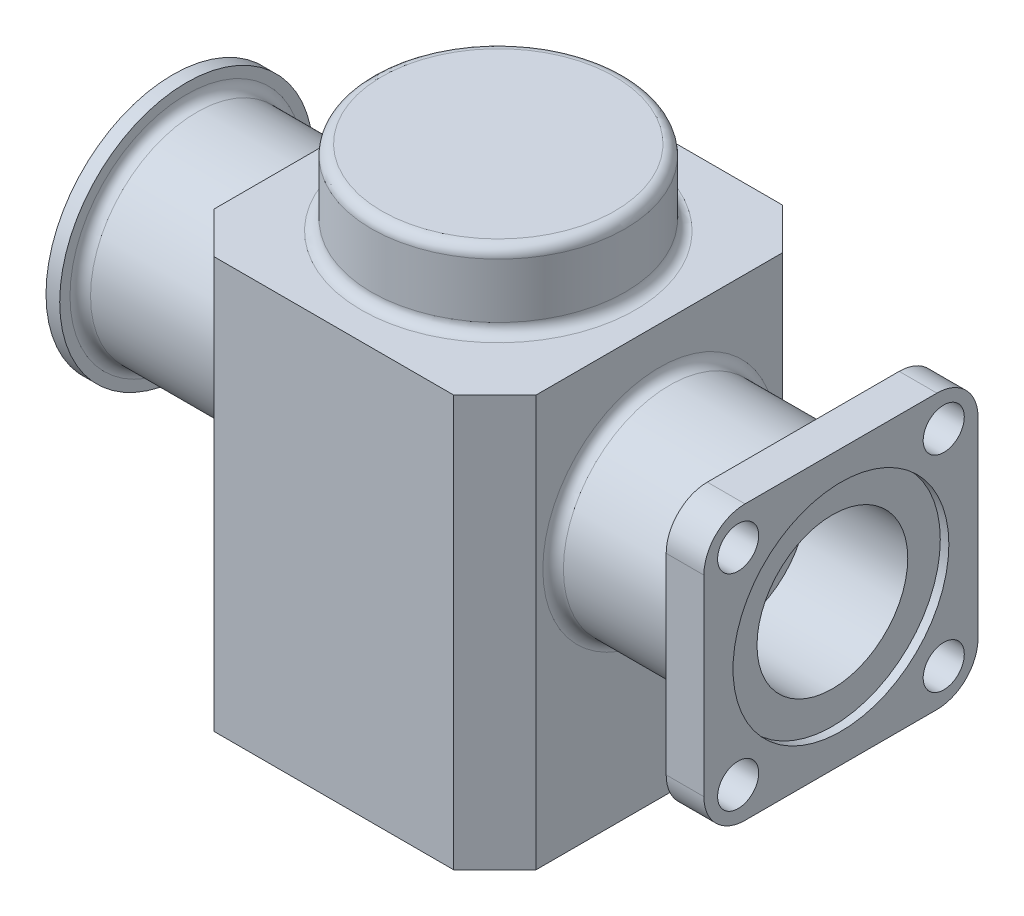
SolidWorks part; units mm, degrees
material "БрА9Мц2Л ГОСТ 493-79"
ref_plane "Спереди" through (0, 0, 0) normal (0, 0, 1) x (1, 0, 0)
ref_plane "Сверху" through (0, 0, 0) normal (0, 1, 0) x (1, 0, 0)
ref_plane "Справа" through (0, 0, 0) normal (1, 0, 0) x (0, 0, -1)
sketch "Эскиз1" plane through (0, 0, 0) normal (0, 1, 0) x (1, 0, 0)
  line L1 (-47, -48) -> (47, -48)
  line L2 (-47, -48) -> (-47, 48)
  line L3 (-47, 48) -> (47, 48)
  line L4 (47, -48) -> (47, 48)
  line L5 (-47, -48) -> (47, 48) construction
  line L6 (-47, 48) -> (47, -48) construction
  circle A0 centre (0, 0) radius 37
  point P0 (0, 0)
  dimension "D3" = 74
  dimension "D1" = 94
  dimension "D2" = 96
extrude "Бобышка-Вытянуть1" add sketch "Эскиз1" against normal blind 120 and the other way blind 22 contours A0 | L1 L4 L3 L2 A0 region at (-45.6564, 0, 0) region at (0, 0, 0)
extrude "Вырез-Вытянуть1" cut sketch "Эскиз1<3>" along normal up to next contours L1 L4 L3 L2 A0 region at (-45.6564, 0, 0)
sketch "Эскиз1<3>" plane through (0, 0, 0) normal (0, 1, 0) x (1, 0, 0) same geometry as "Эскиз1"
sketch "Эскиз2" plane through (0, 0, 0) normal (0, 0, 1) x (1, 0, 0)
  line L0 (-47, -45) -> (47, -45) construction
  line L1 (-47, -120) -> (47, -120) construction
  line L2 (47, 0) -> (47, -120) construction
  line L3 (-47, 0) -> (-47, -120) construction
  line L4 (0, -120) -> (0, 0) construction
  line L8 (89, -14) -> (-91, -14)
  line L9 (-91, -14) -> (-91, -8)
  line L10 (-91, -8) -> (-95, -8)
  line L14 (89, -14) -> (89, -23)
  line L15 (68, -23) -> (68, -30)
  line L16 (68, -30) -> (-56, -30)
  line L17 (68, -23) -> (89, -23)
  line L18 (-56, -30) -> (-56, -21)
  line L20 (-56, -21) -> (-65, -21)
  line L23 (-65, -23.5) -> (-95, -23.5)
  line L24 (-95, -23.5) -> (-95, -8)
  line L25 (-65, -23.5) -> (-65, -21)
  point P13 (-65, -22.25)
  dimension "D1" = 75
  dimension "D2" = 184
  dimension "D3" = 21
  dimension "D4" = 48
  dimension "D5" = 44
  dimension "D6" = 74
  dimension "D7" = 30
  dimension "D8" = 30
  dimension "D9" = 62
  dimension "D10" = 89
  dimension "D11" = 39
  dimension "D12" = 4
  dimension "D13" = 2.5
revolve "Повернуть1" add sketch "Эскиз2" angle 360 about L0
cosmetic thread "Условное изображение резьбы3" parameters "D2"=45
sketch "Эскиз3" plane through (-47, 0, 0) normal (-1, 0, 0) x (0, 0, 1)
  circle A1 centre (0, -45) radius 15
  circle A2 centre (0, -45) radius 15
  dimension "D1" = 0
extrude "Вырез-Вытянуть2" cut sketch "Эскиз3" against normal through all
sketch "Эскиз4" plane through (89, 0, 0) normal (1, 0, 0) x (0, 0, -1)
  line L0 (30, -15) -> (-30, -15) construction
  line L1 (40, -85) -> (40, -5)
  line L2 (40, -5) -> (-40, -5)
  line L3 (-40, -5) -> (-40, -85)
  line L4 (-40, -85) -> (40, -85)
  line L5 (-30, -15) -> (-30, -75) construction
  line L6 (-30, -75) -> (30, -75) construction
  line L7 (30, -75) -> (30, -15) construction
  circle A0 centre (0, -45) radius 40 construction
  circle A1 centre (-30, -15) radius 6
  circle A2 centre (0, -45) radius 15 construction
  circle A3 centre (30, -15) radius 6
  circle A4 centre (30, -75) radius 6
  circle A5 centre (-30, -75) radius 6
  circle A6 centre (0, -45) radius 22 construction
  circle A7 centre (0, -45) radius 22
  point P8 (40, -45)
  dimension "D3" = 12
  dimension "D1" = 80
  dimension "D2" = 10
  dimension "D4" = 2
  dimension "D5" = 2
extrude "Бобышка-Вытянуть2" add sketch "Эскиз4" along normal blind 11
sketch "Эскиз5" plane through (100, 0, 0) normal (1, 0, 0) x (0, 0, -1)
  circle A0 centre (0, -45) radius 31.5
  circle A1 centre (0, -45) radius 15 construction
  dimension "D1" = 63
extrude "Вырез-Вытянуть3" cut sketch "Эскиз5" against normal blind 2.5
sketch "Эскиз6" plane through (0, 0, 0) normal (0, 0, 1) x (1, 0, 0)
  line L0 (0, -120) -> (0, 6)
  line L1 (-47, -120) -> (47, -120) construction
  line L2 (28.5, -85) -> (17.3266, 6)
  line L3 (28.5, -85) -> (32, -85)
  line L4 (32, -85) -> (32, -102)
  line L5 (32, -102) -> (29.5, -102)
  line L6 (29.5, -102) -> (29.5, -120)
  line L7 (17.3266, 6) -> (0, 6)
  line L8 (29.5, -120) -> (0, -120)
  dimension "D1" = 28.5
  dimension "D2" = 126
  dimension "D3" = 32
  dimension "D4" = 18
  dimension "D5" = 35
  dimension "D6" = 2.5
  dimension "D7" = 7
revolve "Вырез-Повернуть2" cut sketch "Эскиз6" angle 360 about L0
cosmetic thread "Условное изображение резьбы5" parameters "D2"=60
fillet "Скругление1" radius 3 6 edges at (-91, -45, 31) (89, -45, 31) (0, 0, 37) (0, 22, 37) (47, -45, 31) (-47, -45, 31)
fillet "Скругление2" radius 12 4 edges at (94.5, -5, -40) (94.5, -5, 40) (94.5, -85, 40) (94.5, -85, -40)
chamfer "Фаска1" distance 12 angle 45 4 edges at (47, -60, -48) (47, -60, 48) (-47, -60, 48) (-47, -60, -48)
chamfer "Фаска2" distance 1.3 angle 45 2 edges at (29.5, -120, 0) (-95, -45, 21.5)
